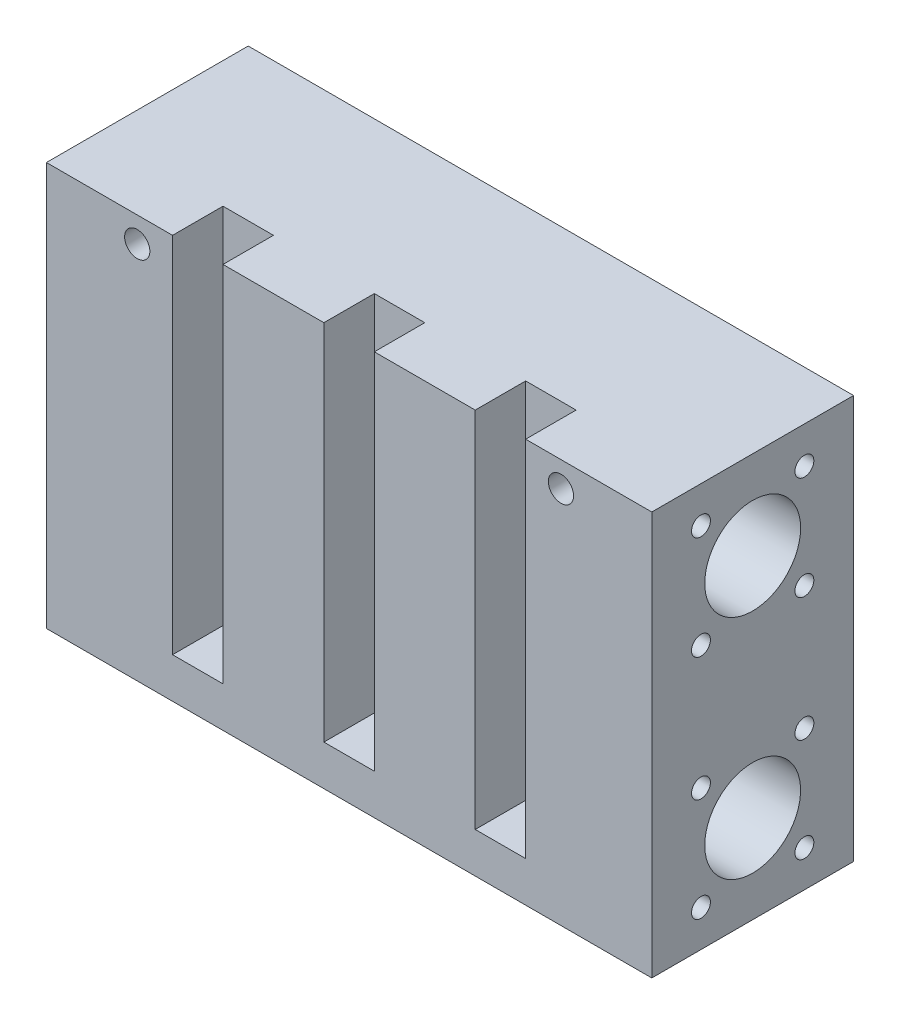
SolidWorks part; units mm, degrees
material "1060 Alloy"
ref_plane "Front Plane" through (0, 0, 0) normal (0, 0, 1) x (1, 0, 0)
ref_plane "Top Plane" through (0, 0, 0) normal (0, 1, 0) x (1, 0, 0)
ref_plane "Right Plane" through (0, 0, 0) normal (1, 0, 0) x (0, 0, -1)
sketch "Sketch1" plane through (0, 0, 0) normal (0, 0, 1) x (1, 0, 0)
  line L1 (0, 0) -> (120, 0)
  line L2 (0, 0) -> (0, 80)
  line L3 (0, 80) -> (120, 80)
  line L4 (120, 0) -> (120, 80)
  dimension "D1" = 80
  dimension "D2" = 120
extrude "Boss-Extrude1" add sketch "Sketch1" along normal blind 40 contours L3 L4 L1 L2
sketch "Sketch2" plane through (0, 0, 0) normal (-1, 0, 0) x (0, 0, 1)
  line L0 (20, 80) -> (20, 0) construction
  line L1 (40, 80) -> (0, 80) construction
  line L2 (40, 0) -> (0, 0) construction
  line L3 (40, 40) -> (0, 40) construction
  line L4 (40, 0) -> (40, 80) construction
  line L5 (0, 0) -> (0, 80) construction
  line L6 (0, 62.5) -> (40, 62.5) construction
  line L7 (0, 17.5) -> (40, 17.5) construction
  circle A1 centre (30.25, 72.75) radius 1.85
  circle A2 centre (9.75, 72.75) radius 1.85
  circle A3 centre (30.25, 52.25) radius 1.85
  circle A4 centre (9.75, 52.25) radius 1.85
  circle A5 centre (9.75, 27.75) radius 1.85
  circle A6 centre (30.25, 27.75) radius 1.85
  circle A7 centre (30.25, 7.25) radius 1.85
  circle A9 centre (9.75, 7.25) radius 1.85
  dimension "D4" = 3.7
  dimension "D1" = 22.5
  dimension "D2" = 9.75
  dimension "D3" = 7.25
extrude "linear-bearing-screw-cuts" cut sketch "Sketch2" against normal blind 14
sketch "Sketch3" plane through (0, 0, 0) normal (-1, 0, 0) x (0, 0, 1)
  line L0 (20, 80) -> (20, 0) construction
  line L1 (40, 80) -> (0, 80) construction
  line L2 (40, 0) -> (0, 0) construction
  line L3 (0, 40) -> (40, 40) construction
  line L4 (0, 0) -> (0, 80) construction
  line L5 (40, 0) -> (40, 80) construction
  line L6 (0, 62.5) -> (40, 62.5) construction
  line L7 (0, 17.5) -> (40, 17.5) construction
  circle A0 centre (20, 62.5) radius 9.5
  circle A2 centre (20, 17.5) radius 9.5
  dimension "D2" = 19
  dimension "D1" = 45
extrude "linear-bearings-hole" cut sketch "Sketch3" against normal blind 55
sketch "Sketch4" plane through (120, 0, 0) normal (1, 0, 0) x (0, 0, -1)
  line L0 (-20, 80) -> (-20, 0) construction
  line L1 (-40, 80) -> (0, 80) construction
  line L2 (-40, 0) -> (0, 0) construction
  line L3 (-40, 40) -> (0, 40) construction
  line L4 (-40, 0) -> (-40, 80) construction
  line L5 (0, 0) -> (0, 80) construction
  line L6 (-40, 62.5) -> (0, 62.5) construction
  line L7 (-40, 17.5) -> (0, 17.5) construction
  circle A0 centre (-9.75, 72.75) radius 1.875
  circle A1 centre (-30.25, 72.75) radius 1.875
  circle A2 centre (-9.75, 52.25) radius 1.875
  circle A3 centre (-30.25, 52.25) radius 1.875
  circle A4 centre (-30.25, 27.75) radius 1.875
  circle A5 centre (-9.75, 27.75) radius 1.875
  circle A6 centre (-9.75, 7.25) radius 1.875
  circle A7 centre (-30.25, 7.25) radius 1.875
  dimension "D2" = 3.75
  dimension "D1" = 45
  dimension "D3" = 7.25
  dimension "D4" = 9.75
extrude "linear-bearing-screw-cuts2" cut sketch "Sketch4" against normal blind 14
sketch "Sketch5" plane through (120, 0, 0) normal (1, 0, 0) x (0, 0, -1)
  line L0 (-20, 80) -> (-20, 0) construction
  line L1 (-40, 80) -> (0, 80) construction
  line L2 (-40, 0) -> (0, 0) construction
  line L3 (0, 40) -> (-40, 40) construction
  line L4 (0, 0) -> (0, 80) construction
  line L5 (-40, 0) -> (-40, 80) construction
  line L6 (-40, 62.5) -> (0, 62.5) construction
  line L7 (-40, 17.5) -> (0, 17.5) construction
  circle A0 centre (-20, 62.5) radius 9.5
  circle A1 centre (-20, 17.5) radius 9.5
  dimension "D2" = 19
  dimension "D1" = 45
extrude "linear-bearings-hole2" cut sketch "Sketch5" against normal blind 55
sketch "Sketch10" plane through (0, 80, 0) normal (0, 1, 0) x (1, 0, 0)
  line L0 (60, 0) -> (60, -40) construction
  line L1 (0, 0) -> (120, 0) construction
  line L2 (0, -40) -> (120, -40) construction
  line L3 (75, 0) -> (75, -40) construction
  line L4 (95, -40) -> (95, -30)
  line L5 (95, -30) -> (85, -30)
  line L6 (85, -30) -> (85, -40)
  line L7 (85, -40) -> (95, -40)
  line L8 (120, -40) -> (120, 0) construction
  line L9 (65, -30) -> (65, -40)
  line L10 (55, -30) -> (65, -30)
  line L11 (55, -40) -> (55, -30)
  line L12 (65, -40) -> (55, -40)
  line L13 (35, -30) -> (35, -40)
  line L14 (25, -30) -> (35, -30)
  line L15 (25, -40) -> (25, -30)
  line L16 (35, -40) -> (25, -40)
  point P10 (90, -40)
  point P23 (97.4542, -37.5004)
  point P24 (85, -40)
  point P25 (95, -37.3154)
  point P26 (85, -37.4335)
  dimension "D1" = 10
  dimension "D3" = 10
  dimension "D4" = 30
  dimension "D5" = 45
extrude "Cut-Extrude7" cut sketch "Sketch10" against normal blind 72
sketch "Sketch11" plane through (0, 0, 40) normal (0, 0, 1) x (1, 0, 0)
  line L0 (0, 0) -> (120, 0) construction
  line L1 (0, 0) -> (0, 80) construction
  line L2 (120, 0) -> (120, 80) construction
  circle A0 centre (5.5, 35) radius 1.25
  circle A1 centre (36.5, 35) radius 1.25
  circle A2 centre (83.5, 35) radius 1.25
  circle A3 centre (114.5, 35) radius 1.25
  circle A4 centre (5.5, 4) radius 1.25
  circle A5 centre (36.5, 4) radius 1.25
  circle A6 centre (83.5, 4) radius 1.25
  circle A7 centre (114.5, 4) radius 1.25
  dimension "D7" = 2.5
  dimension "D1" = 4
  dimension "D2" = 31
  dimension "D3" = 31
  dimension "D4" = 5.5
  dimension "D5" = 31
  dimension "D6" = 5.5
extrude "Cut-Extrude8" [suppressed] cut sketch "Sketch11" against normal through all
sketch "Sketch12" plane through (65, 0, 0) normal (1, 0, 0) x (0, 0, -1)
  circle A0 centre (-20, 62.5) radius 6
  circle A1 centre (-20, 17.5) radius 6
  dimension "D1" = 12
extrude "Cut-Extrude9" cut sketch "Sketch12" against normal through all
sketch "Sketch13" plane through (0, 0, 0) normal (0, 0, -1) x (-1, 0, 0)
  line L0 (0, 80) -> (-120, 80) construction
  line L1 (-120, 0) -> (-120, 80) construction
  line L2 (0, 0) -> (0, 80) construction
  circle A0 centre (-102, 75) radius 2.5
  circle A1 centre (-18, 75) radius 2.5
  point P4 (0, 0)
  point P9 (-14.4347, 75)
  dimension "D4" = 5
  dimension "D1" = 5
  dimension "D2" = 18
  dimension "D3" = 18
extrude "Cut-Extrude10" cut sketch "Sketch13" against normal through all
